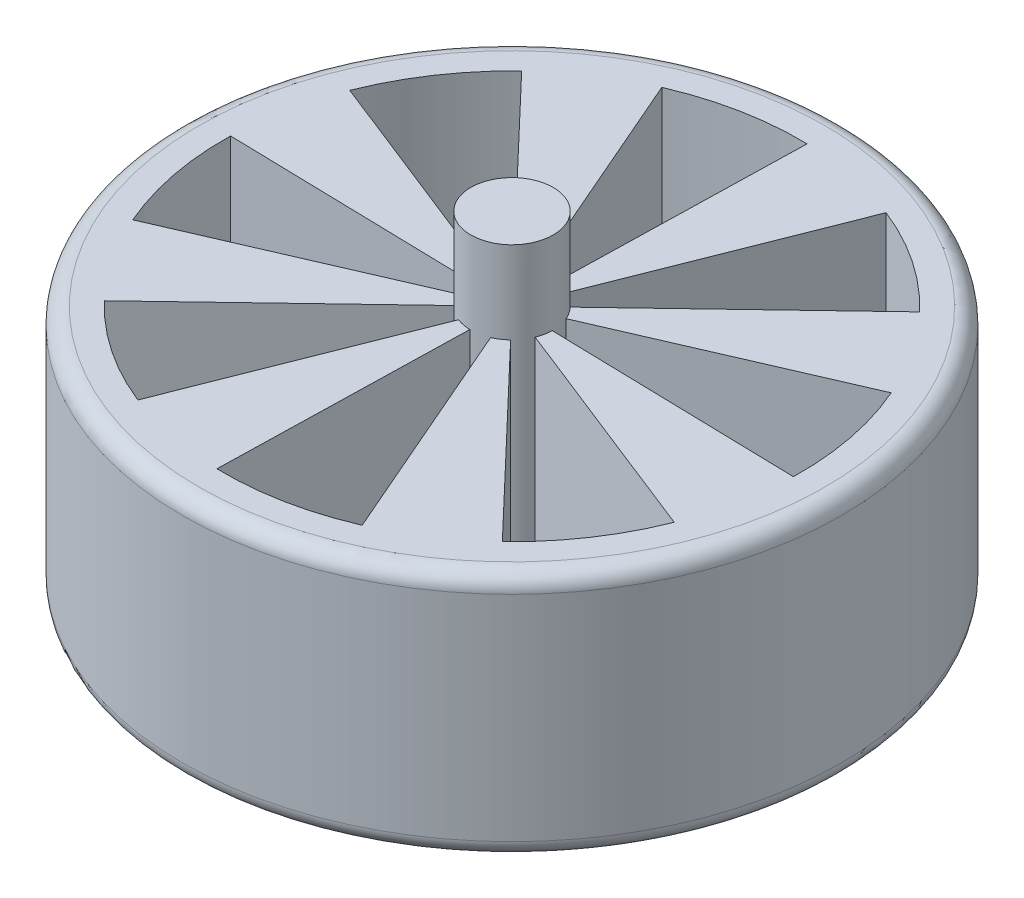
SolidWorks part; units mm, degrees
ref_plane "Front Plane" through (0, 0, 0) normal (0, 0, 1) x (1, 0, 0)
ref_plane "Top Plane" through (0, 0, 0) normal (0, 1, 0) x (1, 0, 0)
ref_plane "Right Plane" through (0, 0, 0) normal (1, 0, 0) x (0, 0, -1)
sketch "Sketch2" plane through (0, 0, 0) normal (0, 1, 0) x (1, 0, 0)
  circle A0 centre (0, 0) radius 101.6
extrude "Boss-Extrude1" add sketch "Sketch2" along normal blind 76.2
sketch "Sketch3" plane through (0, 76.2, 0) normal (0, 1, 0) x (1, 0, 0)
  circle A0 centre (0, 0) radius 12.7
  dimension "D1" = 25.4
sketch "Sketch4" plane through (0, 0, 0) normal (0, -1, 0) x (-1, 0, 0)
  circle A0 centre (0, 0) radius 12.7
extrude "Boss-Extrude4" add sketch "Sketch4" along normal blind 25.4 contours A0
sketch "Sketch5" plane through (0, 76.2, 0) normal (0, 1, 0) x (1, 0, 0)
  line L0 (0, 0) -> (93.2136, 40.4201) construction
  circle A0 centre (0, 0) radius 101.6 construction
sketch "Sketch6" plane through (0, 76.2, 0) normal (0, 1, 0) x (1, 0, 0)
  line L0 (0, 0) -> (77.798, 43.0196)
  line L1 (0, 0) -> (88.8848, -1.6429)
  line L2 (0, 0) -> (85.4309, -24.592)
  line L3 (0, 0) -> (61.6894, -64.0128)
  line L4 (0, 0) -> (43.0196, -77.798)
  line L5 (0, 0) -> (-1.6429, -88.8848)
  line L6 (0, 0) -> (-24.592, -85.4309)
  line L7 (0, 0) -> (-64.0128, -61.6894)
  line L8 (0, 0) -> (-77.798, -43.0196)
  line L9 (0, 0) -> (-88.8848, 1.6429)
  line L10 (0, 0) -> (-85.4309, 24.592)
  line L11 (0, 0) -> (-61.6894, 64.0128)
  line L12 (0, 0) -> (-43.0196, 77.798)
  line L13 (0, 0) -> (1.6429, 88.8848)
  line L14 (0, 0) -> (24.592, 85.4309)
  line L15 (0, 0) -> (64.0128, 61.6894)
  arc A0 (77.798, 43.0196) -> (88.8848, -1.6429) centre (0, 0) cw
  arc A1 (85.4309, -24.592) -> (61.6894, -64.0128) centre (0, 0) cw
  arc A2 (43.0196, -77.798) -> (-1.6429, -88.8848) centre (0, 0) cw
  arc A3 (-24.592, -85.4309) -> (-64.0128, -61.6894) centre (0, 0) cw
  arc A4 (-77.798, -43.0196) -> (-88.8848, 1.6429) centre (0, 0) cw
  arc A5 (-85.4309, 24.592) -> (-61.6894, 64.0128) centre (0, 0) cw
  arc A6 (-43.0196, 77.798) -> (1.6429, 88.8848) centre (0, 0) cw
  arc A7 (24.592, 85.4309) -> (64.0128, 61.6894) centre (0, 0) cw
  point P22 (0, 0)
  dimension "D1" = 30
  dimension "D2" = 8
fillet "Fillet1" radius 5.08 1 edges at (0, 76.2, 101.6)
fillet "Fillet2" radius 5.08 1 edges at (0, 0, 101.6)
sketch "Sketch7" plane through (0, 0, 0) normal (0, -1, 0) x (1, 0, 0)
  line L0 (0, 0) -> (81.5619, -35.3676)
  line L1 (0, 0) -> (93.2136, -40.4201) construction
  line L2 (0, 0) -> (88.875, 2.1083)
  line L3 (0, 0) -> (64.3349, -61.3533)
  line L4 (0, 0) -> (32.6643, -82.6816)
  line L5 (0, 0) -> (2.1083, -88.875)
  line L6 (0, 0) -> (-35.3676, -81.5619)
  line L7 (0, 0) -> (-61.3533, -64.3349)
  line L8 (0, 0) -> (-82.6816, -32.6643)
  line L9 (0, 0) -> (-88.875, -2.1083)
  line L10 (0, 0) -> (-81.5619, 35.3676)
  line L11 (0, 0) -> (-64.3349, 61.3533)
  line L12 (0, 0) -> (-32.6643, 82.6816)
  line L13 (0, 0) -> (-2.1083, 88.875)
  line L14 (0, 0) -> (35.3676, 81.5619)
  line L15 (0, 0) -> (61.3533, 64.3349)
  line L16 (0, 0) -> (82.6816, 32.6643)
  arc A0 (88.875, 2.1083) -> (81.5619, -35.3676) centre (0, 0) cw
  arc A1 (64.3349, -61.3533) -> (32.6643, -82.6816) centre (0, 0) cw
  arc A2 (2.1083, -88.875) -> (-35.3676, -81.5619) centre (0, 0) cw
  arc A3 (-61.3533, -64.3349) -> (-82.6816, -32.6643) centre (0, 0) cw
  arc A4 (-88.875, -2.1083) -> (-81.5619, 35.3676) centre (0, 0) cw
  arc A5 (-64.3349, 61.3533) -> (-32.6643, 82.6816) centre (0, 0) cw
  arc A6 (-2.1083, 88.875) -> (35.3676, 81.5619) centre (0, 0) cw
  arc A7 (61.3533, 64.3349) -> (82.6816, 32.6643) centre (0, 0) cw
  point P24 (0, 0)
  circle M11 centre (0, 0) radius 12.7
  dimension "D1" = 24.802
  dimension "D2" = 8
extrude "Cut-Extrude2" cut sketch "Sketch7" against normal blind 76.2 contours A4 L9 L10 M11 | A5 L11 L12 M11 | A6 L13 L14 M11 | A7 L15 L16 M11 | A0 L2 L0 M11 | A1 L3 L4 M11 | A2 L5 L6 M11 | A3 L7 L8 M11 region at (58.747, 0, -11.4639) region at (33.4342, 0, -49.6467) region at (-11.4639, 0, -58.747) region at (-49.6467, 0, -33.4342) region at (-58.747, 0, 11.4639) region at (-33.4342, 0, 49.6467) region at (11.4639, 0, 58.747) region at (49.6467, 0, 33.4342)
sketch "Sketch8" plane through (0, 76.2, 0) normal (0, 1, 0) x (1, 0, 0)
  circle A0 centre (0, 0) radius 12.7
extrude "Boss-Extrude5" add sketch "Sketch8" along normal blind 25.4
